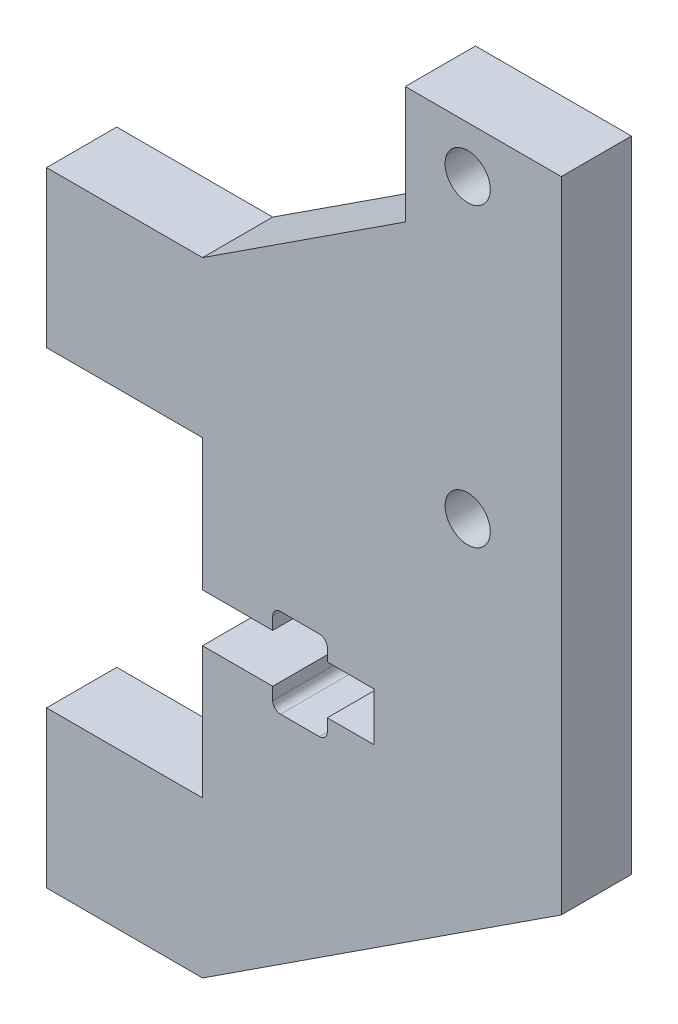
SolidWorks part; units mm, degrees
ref_plane "Front Plane" through (0, 0, 0) normal (0, 0, 1) x (1, 0, 0)
ref_plane "Top Plane" through (0, 0, 0) normal (0, 1, 0) x (1, 0, 0)
ref_plane "Right Plane" through (0, 0, 0) normal (1, 0, 0) x (0, 0, -1)
sketch "Sketch1" plane through (0, 0, 0) normal (0, 0, 1) x (1, 0, 0)
  line L0 (13, 3.4783) -> (0, -5)
  line L1 (0, -5) -> (-10, -5)
  line L2 (-10, -5) -> (-10, -15)
  line L3 (-10, -15) -> (0, -15)
  line L4 (0, -15) -> (0, -35)
  line L5 (0, -35) -> (-10, -35)
  line L6 (-10, -35) -> (-10, -45)
  line L7 (-10, -45) -> (0, -45)
  line L10 (0, -45) -> (23, -30)
  line L11 (23, -30) -> (23, 11)
  line L12 (23, 11) -> (13, 11)
  line L13 (13, 11) -> (13, 3.4783)
  line L15 (0, -5) -> (0, -45) construction
  line L16 (-10, -10) -> (0, -10) construction
  line L17 (-10, -40) -> (0, -40) construction
  line L18 (-10, -15) -> (-10, -35) construction
  line L19 (-10, -25) -> (0, -25) construction
  dimension "D1" = 10
  dimension "D2" = 10
  dimension "D3" = 10
  dimension "D4" = 10
  dimension "D5" = 15
  dimension "D8" = 10
  dimension "D10" = 13
  dimension "D6" = 15
  dimension "D7" = 16
extrude "Boss-Extrude1" add sketch "Sketch1" along normal blind 4.5
sketch "Sketch2" plane through (0, 0, 4.5) normal (0, 0, 1) x (1, 0, 0)
  line L0 (0, -25) -> (23, -25) construction
  line L1 (0, -15) -> (0, -35) construction
  line L3 (11, -26.55) -> (11, -23.45) construction
  line L4 (11, -23.45) -> (0, -23.45) construction
  line L5 (0, -26.55) -> (0, -23.45)
  line L6 (0, -23.45) -> (4.5, -23.45)
  line L7 (4.5, -23.45) -> (4.5, -22.65)
  line L8 (5, -22.15) -> (7.5, -22.15)
  line L9 (8, -22.65) -> (8, -23.45)
  line L10 (8, -23.45) -> (11, -23.45)
  line L11 (11, -23.45) -> (11, -26.55)
  line L12 (11, -26.55) -> (0, -26.55) construction
  line L13 (8, -26.55) -> (11, -26.55)
  line L14 (8, -27.35) -> (8, -26.55)
  line L15 (5, -27.85) -> (7.5, -27.85)
  line L16 (4.5, -26.55) -> (4.5, -27.35)
  line L17 (0, -26.55) -> (4.5, -26.55)
  line L18 (23, -30) -> (23, 11) construction
  arc A0 (7.5, -22.15) -> (8, -22.65) centre (7.5, -22.65) cw
  arc A1 (4.5, -22.65) -> (5, -22.15) centre (5, -22.65) cw
  arc A2 (4.5, -27.35) -> (5, -27.85) centre (5, -27.35) ccw
  arc A3 (7.5, -27.85) -> (8, -27.35) centre (7.5, -27.35) ccw
  point P15 (8, -22.15)
  point P18 (4.5, -22.15)
  point P27 (11, -25)
  point P29 (4.5, -27.85)
  point P30 (8, -27.85)
  dimension "D6" = 0.5
  dimension "D1" = 11
  dimension "D2" = 1.55
  dimension "D3" = 8
  dimension "D4" = 3.5
  dimension "D5" = 2.85
extrude "screw-cutout" cut sketch "Sketch2" against normal through all
sketch "Sketch3" plane through (0, 0, 4.5) normal (0, 0, 1) x (1, 0, 0)
  line L0 (17, 55) -> (17, -45) construction
  line L3 (13, 11) -> (13, 3.4783) construction
  line L5 (-10, -45) -> (0, -45) construction
  line L10 (11, -26.55) -> (11, -23.45) construction
  circle A1 centre (17, 8) radius 1.45
  circle A5 centre (17, -11) radius 1.45
  point P8 (11, -25)
  dimension "D4" = 2.9
  dimension "D11" = 2.9
  dimension "D6" = 4
  dimension "D12" = 19
  dimension "D2" = 14
extrude "Cut-Extrude2" cut sketch "Sketch3" against normal through all
sketch "Sketch4" [suppressed] plane through (0, 0, 4.5) normal (0, 0, 1) x (1, 0, 0)
  line L0 (17, -11) -> (17, 8) construction
  line L1 (17, -1.5) -> (13, -1.5) construction
  line L2 (13, 11) -> (13, 3.4783) construction
  line L4 (15, 2.5) -> (13, 2.5)
  line L5 (15, 2.5) -> (15, -5.5)
  line L6 (15, -5.5) -> (13, -5.5)
  line L7 (13, 2.5) -> (13, -5.5)
  line L8 (15, 2.5) -> (13, -5.5) construction
  line L9 (15, -5.5) -> (13, 2.5) construction
  circle A1 centre (17, 8) radius 1.55 construction
  circle A3 centre (17, -11) radius 1.55 construction
  point P11 (14, -1.5)
  dimension "D1" = 8
  dimension "D2" = 2
  dimension "D3" = 3
equation "\"X-ROD-SPACING\"=45"
equation "\"Y-ROD-SPACING\"=75"
equation "\"Z-ROD-SPACING\"=17.5"
equation "\"Y-BED-OFFSET\"=2"
equation "\"Y-BED-ROD-INSET\"=3.5"
equation "\"T-SLOT-NUT-FILLET-RADIUS\"=0.5"
equation "\"T-SLOT-SCREW-SHAFT-RADIUS\"=1.55"
equation "\"T-SLOT-SCREW-SHAFT-CUTOUT-LENGTH\"=11"
equation "\"T-SLOT-NUT-DEPTH\"=3.5"
equation "\"T-SLOT-NUT-WIDTH\"=2.85"
equation "\"T-SLOT-NUT-END-DISTANCE\"=8"
equation "\"ACRYLIC-THICKNESS\"=10"
equation "\"ACRYLIC-THICKNESS2\"=4.5"
equation "\"ACRYLIC-TAB-CUTOUT-SIZE\"=\"ACRYLIC-THICKNESS\"+\"ACRYLIC-TAB-TOLERANCE\"*2"
equation "\"ACRYLIC-TAB-WIDTH\"=\"ACRYLIC-THICKNESS\""
equation "\"ACRYLIC-M3-HOLE\"=2.9"
equation "\"SMOOTHROD-CAP-SCREW-DISTANCE\"=20"
equation "\"FRAME-WIDTH-INNER\"=370"
equation "\"NEMA17-HOLE-SPACING\"=31"
equation "\"NEMA17-CENTRAL-CUTOUT\"=22.5"
equation "\"Z-BRACKET-REACH\"=55"
equation "\"Z-ROD-INSET\"=13.5"
equation "\"TOP-BRACKET-SPACING\"=40"
equation "\"SMOOTHROD-X-LENGTH\"=350"
equation "\"SMOOTHROD-Y-LENGTH\"=350"
equation "\"SMOOTHROD-Z-LENGTH\"=350"
equation "\"SMOOTHROD-TIGHTENING-HEADROOM\"=.25"
equation "\"LEADSCREW-Z-LENGTH\"=300"
equation "\"SCREW-LENGTH-FRAME\"=\"ACRYLIC-THICKNESS\" + 10"
equation "\"SCREW-HEAD-RADIUS\"=6"
equation "\"PRINTED-X-SMOOTHROD-DIAMETER\"=9.0"
equation "\"PRINTED-X-SMOOTHROD-CUTOUT\"=10"
equation "\"PRINTED-X-BASE-HEIGHT\"=10"
equation "\"PRINTED-LM8UU-CUTOUT-SIZE\"=15.5"
equation "\"PRINTED-LM8UU-CUTOUT-LENGTH\"=24.5"
equation "\"PRINTED-X-IDLER-HEIGHT\"=16"
equation "\"PSU-MOUNTING-WIDTH\"=95"
equation "\"PSU-MOUNTING-HEIGHT\"=177"
equation "\"Y-BELT-TO-ROD-DISTANCE\"=20"
equation "\"SPOOL-HOLDER-ROD-SPACING\"=150"
equation "\"D1@Sketch1\"=\"ACRYLIC-TAB-WIDTH\""
equation "\"D2@Sketch1\"=\"ACRYLIC-TAB-WIDTH\""
equation "\"D3@Sketch1\"=\"ACRYLIC-THICKNESS\""
equation "\"D4@Sketch1\"=\"ACRYLIC-THICKNESS\""
equation "\"D1@Boss-Extrude1\"=\"ACRYLIC-THICKNESS2\""
equation "\"D1@Sketch2\"=\"T-SLOT-SCREW-SHAFT-CUTOUT-LENGTH\""
equation "\"D2@Sketch2\"=\"T-SLOT-SCREW-SHAFT-RADIUS\""
equation "\"D3@Sketch2\"=\"T-SLOT-NUT-END-DISTANCE\""
equation "\"D4@Sketch2\"=\"T-SLOT-NUT-DEPTH\""
equation "\"D5@Sketch2\"=\"T-SLOT-NUT-WIDTH\""
equation "\"D6@Sketch2\"=\"T-SLOT-NUT-FILLET-RADIUS\""
equation "\"D4@Sketch3\"=\"ACRYLIC-M3-HOLE\""
equation "\"D11@Sketch3\"=\"ACRYLIC-M3-HOLE\""
equation "\"Y-BED-SCREW-SPACING\"=209"
equation "\"Y-BED-SCREW-CUTOUT-SLOT-HEIGHT\"=2"
equation "\"ACRYLIC-TAB-TOLERANCE\"=-.05"
equation "\"SCREW-LENGTH-MOTOR\"=\"ACRYLIC-THICKNESS\" + 5"
equation "\"SCREW-LENGTH-EXTRUDER\"=28"
equation "\"PRINTED-M3-HOLE\"=3.5"
equation "\"ACRYLIC-X-CARRIAGE-WIDTH\"=55"
equation "\"ACRYLIC-X-CARRIAGE-HEIGHT\"=75"
equation "\"ACRYLIC-X-CARRIAGE-LM8UU-CUTOUT-WIDTH\"=24.25"
equation "\"ACRYLIC-X-CARRIAGE-LM8UU-CUTOUT-HEIGHT\"=11.0"
equation "\"ACRYLIC-X-CARRIAGE-SCREW-SPACING-X\"=15"
equation "\"ACRYLIC-X-CARRIAGE-SCREW-SPACING-Y\"=33"
equation "\"ACRYLIC-X-CARRIAGE-CENTER-TAB-SPACING\"=14"
equation "\"ACRYLIC-X-CARRIAGE-EXTRUDER-OFFSET\"=26"
equation "\"ACRYLIC-X-CARRIAGE-EXTRUDER-ANGLE\"=90"
equation "\"ACRYLIC-X-CARRIAGE-EXTRUDER-SHELF-DEPTH\"=\"ACRYLIC-X-CARRIAGE-EXTRUDER-OFFSET\" + 28"
equation "\"ACRYLIC-X-CARRIAGE-EXTRUDER-BRACE-SPACING\"=23"
equation "\"ACRYLIC-X-CARRIAGE-EXTRUDER-BRACE-TAB-OFFSET\"=20"
equation "\"ACRYLIC-X-CARRIAGE-EXTRUDER-BRACE-HEIGHT\"=35"
equation "\"ACRYLIC-X-CARRIAGE-EXTRUDER-BRACE-SCREW-SPACING\"=22"
equation "\"ACRYLIC-X-CARRIAGE-DUAL-WIDTH-MULTIPLIER\"=1.65"
equation "\"ACRYLIC-X-CARRIAGE-DUAL-HOTEND-SPACING\"=42"
equation "\"ACRYLIC-X-CARRIAGE-DUAL-WIDTH\"=75"
equation "\"ACRYLIC-X-CARRIAGE-DUAL-HOTEND-SEPARATION\"=36"
equation "\"ACRYLIC-X-CARRIAGE-DUAL-MOUNT-PLATE-DEPTH\"=75"
equation "\"ACRYLIC-X-CARRIAGE-DUAL-MOUNT-BRACE-WIDTH\"=33"
equation "\"ACRYLIC-X-CARRIAGE-DUAL-MOUNT-SCREW-WIDTH\"=40"
equation "\"BLOWER-FAN-WIDTH\"=15"
